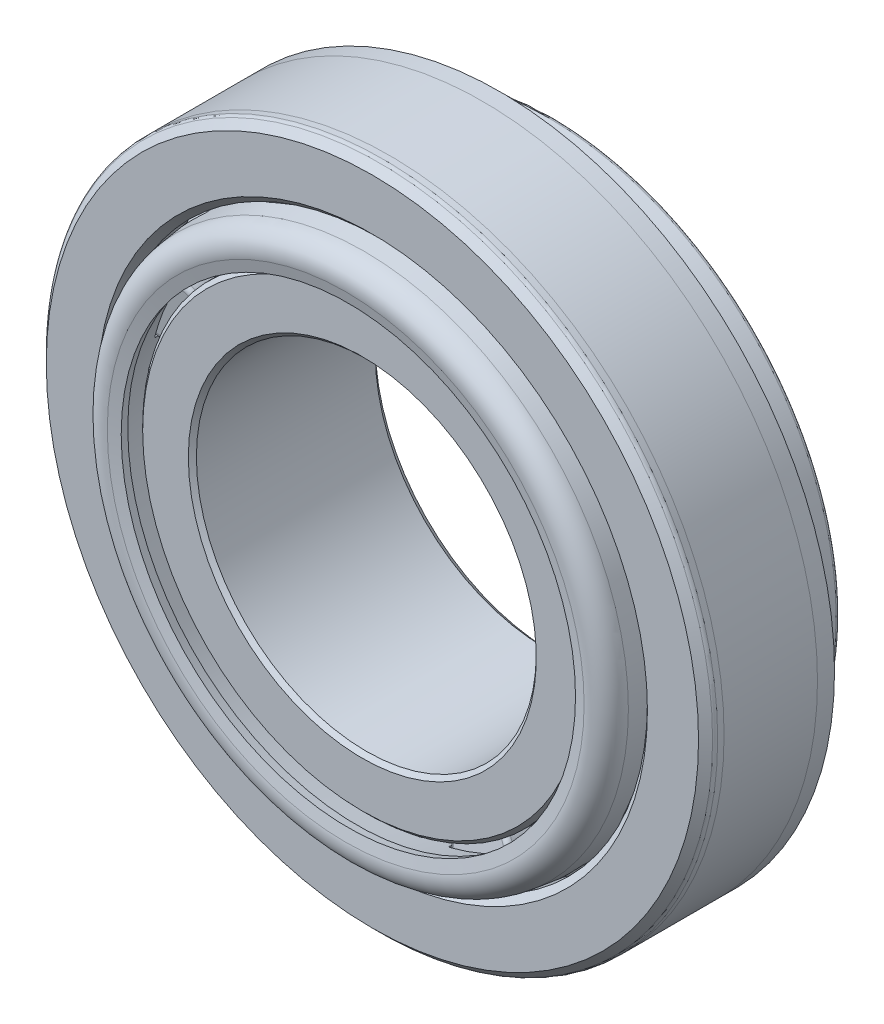
SolidWorks part; units mm, degrees
ref_plane "Front Plane" through (0, 0, 0) normal (0, 0, 1) x (1, 0, 0)
ref_plane "Top Plane" through (0, 0, 0) normal (0, 1, 0) x (1, 0, 0)
ref_plane "Right Plane" through (0, 0, 0) normal (1, 0, 0) x (0, 0, -1)
sketch "Sketch1" plane through (0, 0, 0) normal (1, 0, 0) x (0, 0, -1)
  line L0 (-4.7625, 25.0063) -> (-4.7625, 19.915)
  line L1 (-4.7625, 19.915) -> (4.7625, 22.47)
  line L2 (4.7625, 22.47) -> (4.7625, 25.0063)
  line L3 (4.7625, 25.0063) -> (-4.7625, 25.0063)
  line L4 (0, 0) -> (10110.1541, 0) construction
  line L5 (0.2368, 21.256) -> (5.9385, 0) construction
  line L6 (8.7325, 18.525) -> (8.7325, 12.7)
  line L7 (8.7325, 12.7) -> (-5.5169, 12.7)
  line L8 (-5.5169, 12.7) -> (-5.5169, 16.715)
  line L9 (-5.5169, 16.715) -> (-3.3582, 16.715)
  line L10 (8.7325, 18.525) -> (5.0405, 18.525)
  line L12 (8.7325, 25.0063) -> (-6.7869, 25.0063) construction
  line L14 (-6.7869, 17.938) -> (8.5559, 21.5503)
  line L15 (8.5559, 21.5503) -> (8.7071, 20.9079)
  line L16 (8.7071, 20.9079) -> (-5.9932, 17.4468)
  line L17 (-5.9932, 17.4468) -> (-5.9176, 17.1256)
  line L18 (-4.1503, 20.0792) -> (4.1503, 22.3058) construction
  line L19 (-6.7869, 17.938) -> (-6.56, 16.9743)
  line L20 (-6.56, 16.9743) -> (-5.9176, 17.1256)
  line L21 (4.1503, 22.3058) -> (5.3673, 17.1371)
  line L22 (5.3673, 17.1371) -> (-3.0549, 15.4264)
  line L23 (-3.0549, 15.4264) -> (-4.1503, 20.0792)
  line L25 (-3.6026, 17.7528) -> (4.7588, 19.7215) construction
  line L27 (0, 21.1925) -> (0.5781, 18.7371) construction
  line L28 (0.5781, 18.7371) -> (1.1562, 16.2818) construction
  line L29 (-6.7869, 25.0063) -> (-6.7869, 17.938) construction
  point P7 (0, 25.0063)
  point P44 (4.7015, 19.9648)
  dimension "Width" = 9.525
  dimension "Inner Ring Width" = 14.2494
  dimension "Effective Center" = 2.794
  dimension "Width A" = 13.495
  dimension "Cone Thick" = 0.66
  dimension "D17" = 0.33
  dimension "Roller S Diameter" = 4.78
  dimension "Roller L Diameter" = 5.31
  dimension "Roller Length" = 8.59
  dimension "D2" = 0.25
  dimension "Back Cone Dim" = 0.0254
  dimension "Diameter B" = 39.83
  dimension "Diameter C" = 33.43
  dimension "Diameter F" = 44.94
  dimension "Diameter E" = 37.05
  dimension "D3" = 15.5194
  dimension "ID" = 25.4
  dimension "OD" = 50.0126
  dimension "Cage Width" = 15.5194
sketch "Sketch0" plane through (0, 0, 0) normal (0, 0, 1) x (1, 0, 0)
  circle A0 centre (0, 0) radius 12.7
  circle A1 centre (0, 0) radius 25.0063
  dimension "D1" = 50.0126
  dimension "D2" = 25.4
sketch "Sketch2" plane through (0, 0, 0) normal (1, 0, 0) x (0, 0, -1)
  line L0 (-4.7625, 25.0063) -> (-4.7625, 19.915)
  line L1 (-4.7625, 19.915) -> (4.7625, 22.47)
  line L2 (4.7625, 22.47) -> (4.7625, 25.0063)
  line L3 (4.7625, 25.0063) -> (-4.7625, 25.0063)
revolve "Revolve1" add sketch "Sketch2" angle 360 about L4
sketch "Sketch3" plane through (0, 0, 0) normal (1, 0, 0) x (0, 0, -1)
  line L0 (-5.5169, 16.715) -> (-5.5169, 12.7)
  line L1 (-5.5169, 12.7) -> (8.7325, 12.7)
  line L2 (8.7325, 12.7) -> (8.7325, 18.525)
  line L3 (8.7325, 18.525) -> (5.0405, 18.525)
  line L4 (5.0405, 18.525) -> (5.3673, 17.1371)
  line L5 (5.3673, 17.1371) -> (-3.0549, 15.4264)
  line L6 (-3.0549, 15.4264) -> (-3.3582, 16.715)
  line L7 (-3.3582, 16.715) -> (-5.5169, 16.715)
revolve "Revolve2" add sketch "Sketch3" angle 360 about L4
sketch "Sketch4" plane through (0, 0, 0) normal (1, 0, 0) x (0, 0, -1)
  line L0 (8.7071, 20.9079) -> (8.5559, 21.5503)
  line L1 (8.5559, 21.5503) -> (-7.165, 19.5439)
  line L2 (-7.165, 19.5439) -> (-6.56, 16.9743)
  line L3 (-6.56, 16.9743) -> (-5.9176, 17.1256)
  line L4 (-5.9176, 17.1256) -> (-5.9932, 17.4468)
  line L5 (-5.9932, 17.4468) -> (8.7071, 20.9079)
  line L6 (-4.1503, 20.0792) -> (-6.7869, 17.938) construction
  line L7 (-5.4686, 19.0086) -> (-4.1503, 20.0792) construction
  point P14 (-4.8095, 19.5439)
revolve "Revolve3" add sketch "Sketch4" angle 360 about L4
sketch "Sketch6" plane through (0, 0, 0) normal (1, 0, 0) x (0, 0, -1)
  line L0 (5.3673, 17.1371) -> (4.7588, 19.7215)
  line L1 (4.7588, 19.7215) -> (-3.6026, 17.7528)
  line L3 (-3.6026, 17.7528) -> (-3.0549, 15.4264)
  line L4 (-3.0549, 15.4264) -> (5.3673, 17.1371)
  line L5 (-3.6026, 17.7528) -> (4.7588, 19.7215) construction
  line L6 (-3.0549, 15.4264) -> (-4.1503, 20.0792) construction
revolve "Revolve4" add sketch "Sketch6" angle 360 about L25
sketch "Sketch8" plane through (0, 2.0974, -8.9083) normal (0, 0.2292, -0.9734) x (-1, 0, 0)
  line L0 (0, 15.451) -> (0, 18.106) construction
  circle A0 centre (0, 18.106) radius 1.3275
  point P3 (0, 16.7785)
extrude "Cut-Extrude1" cut sketch "Sketch8" against normal blind 0.635
fillet "Fillet7" radius 0.9525 1 edges at (0, 20.8681, -3.8365)
chamfer "Chamfer4" distance 0.3319 angle 45 1 edges at (0, 17.1371, -5.3673)
fillet "Fillet8" radius 0.3585 1 edges at (0, 15.4264, 3.0549)
pattern_circular "CirPattern1" count 16 over 360 about axis through (0, 0, 0) along (0, 0, 1) of "Revolve4"
fillet "Fillet9" radius 1.6 1 edges at (19.5439, 0, 7.165)
fillet "Fillet10" radius 0.2145 2 edges at (21.5503, 0, -8.5559) (20.9079, 0, -8.7071)
sketch "Sketch9" plane through (0, 0, 0) normal (1, 0, 0) x (0, 0, -1)
  line L0 (-3.6026, 17.7528) -> (4.7588, 19.7215)
  line L1 (4.7588, 19.7215) -> (5.4084, 16.9626)
  line L2 (5.4084, 16.9626) -> (-3.0138, 15.2519)
  line L3 (-3.0138, 15.2519) -> (-3.6026, 17.7528)
  line L4 (-3.0549, 15.4264) -> (5.3673, 17.1371) construction
  dimension "D1" = 0.1793
revolve "Cut-Revolve2" cut sketch "Sketch9" angle 360 about L0
fillet "Fillet11" radius 0.239 4 edges at (-2.2221, 19.0084, 3.8982) (2.2221, 19.0084, 3.8982) (2.7631, 20.3361, -4.6141) (-2.7631, 20.3361, -4.6141)
pattern_circular "CirPattern2" count 16 over 360 about axis through (0, 0, 0) along (0, 0, 1) of "Cut-Revolve2", "Fillet11"
chamfer "Chamfer1" distance 0.6364 angle 45 2 edges at (25.0063, 0, 4.7625) (19.915, 0, 4.7625)
ref_plane "Plane1" through (0, 0, 3.4897) normal (0, 0, 1) x (1, 0, 0)
ref_plane "Plane2" through (0, 0, -3.4897) normal (0, 0, -1) x (-1, 0, 0)
split line "Split Line1"
split line "Split Line2"
fillet "Fillet6" radius 0.3818 1 edges at (-25.0063, 0, 4.1261)
chamfer "Chamfer2" distance 0.3011 angle 45 2 edges at (16.715, 0, 5.5169) (12.7, 0, 5.5169)
chamfer "Chamfer3" distance 0.5825 angle 45 2 edges at (12.7, 0, -8.7325) (18.525, 0, -8.7325)
sketch "Sketch7" plane through (0, 0, 0) normal (1, 0, 0) x (0, 0, -1)
  line L0 (8.7325, 18.525) -> (8.7325, 12.7) construction
  line L1 (-5.5169, 16.715) -> (-3.3582, 16.715) construction
  line L2 (-5.5169, 12.7) -> (-5.5169, 16.715) construction
  line L3 (8.7325, 12.7) -> (-5.5169, 12.7) construction
  line L4 (8.7325, 18.525) -> (5.0405, 18.525) construction
  line L5 (5.3673, 17.1371) -> (-3.0549, 15.4264) construction
  line L6 (4.1503, 22.3058) -> (5.3673, 17.1371) construction
  line L7 (-4.7625, 19.915) -> (4.7625, 22.47) construction
  line L8 (-3.0549, 15.4264) -> (-4.1503, 20.0792) construction
  line L9 (8.7325, 18.525) -> (8.7325, 12.7)
  line L10 (-5.5169, 16.715) -> (-3.3582, 16.715)
  line L11 (-5.5169, 12.7) -> (-5.5169, 16.715)
  line L12 (8.7325, 12.7) -> (-5.5169, 12.7)
  line L13 (8.7325, 18.525) -> (5.0405, 18.525)
  line L14 (5.3673, 17.1371) -> (-3.0549, 15.4264)
  line L15 (4.1503, 22.3058) -> (5.3673, 17.1371)
  line L16 (-4.1503, 20.0792) -> (4.1503, 22.3058)
  line L17 (-3.0549, 15.4264) -> (-4.1503, 20.0792)
  line L18 (0, 0) -> (8.7325, 0) construction
  line L21 (-3.0549, -15.4264) -> (-4.1503, -20.0792)
  line L22 (-4.1503, -20.0792) -> (4.1503, -22.3058)
  line L23 (4.1503, -22.3058) -> (5.3673, -17.1371)
  line L24 (5.3673, -17.1371) -> (-3.0549, -15.4264)
  line L25 (8.7325, -18.525) -> (5.0405, -18.525)
  line L26 (8.7325, -12.7) -> (-5.5169, -12.7)
  line L27 (-5.5169, -12.7) -> (-5.5169, -16.715)
  line L28 (-5.5169, -16.715) -> (-3.3582, -16.715)
  line L29 (8.7325, -18.525) -> (8.7325, -12.7)
equation "\"D17@Sketch1\" = \"Cone Thick@Sketch1\" / 2"
equation "\"D1@Chamfer1\"=(\"OD@Sketch1\"-\"Diameter B@Sketch1\")*0.5*0.125"
equation "\"D1@Plane1\"=(\"OD@Sketch1\"-\"Diameter B@Sketch1\")*0.5*0.25"
equation "\"D1@Plane2\"=(\"OD@Sketch1\"-\"Diameter B@Sketch1\")*0.5*0.25"
equation "\"D1@Fillet6\"=(\"OD@Sketch1\"-\"Diameter B@Sketch1\")*0.5*0.075"
equation "\"D1@Chamfer2\"=(\"Diameter C@Sketch1\"-\"ID@Sketch1\")*0.5*0.075"
equation "\"D1@Chamfer3\"=(\"Diameter E@Sketch1\"-\"ID@Sketch1\")*0.5*0.1"
equation "\"D1@Chamfer4\"=\"Roller L Diameter@Sketch1\"*0.0625"
equation "\"D1@Fillet8\"=\"Roller S Diameter@Sketch1\"*0.075"
equation "\"D1@Fillet9\"=(\"Diameter B@Sketch1\"-\"Diameter C@Sketch1\")*0.5*0.5"
equation "\"D1@Fillet10\"=\"Cone Thick@Sketch1\"*0.325"
equation "\"D1@Sketch9\"=\"Roller S Diameter@Sketch1\"*0.0375"
equation "\"D1@Fillet11\"=\"Roller S Diameter@Sketch1\"*0.05"
equation "\"D1@CirPattern2\"=\"Number of Rollers@CirPattern1\""
